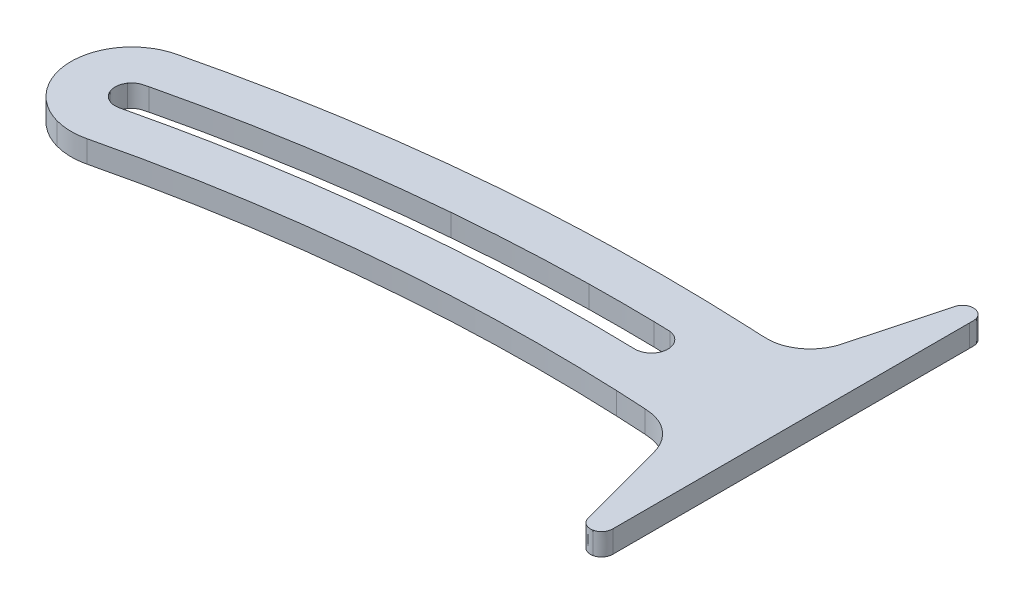
SolidWorks part; units mm, degrees
ref_plane "Front Plane" through (0, 0, 0) normal (0, 0, 1) x (1, 0, 0)
ref_plane "Top Plane" through (0, 0, 0) normal (0, 1, 0) x (1, 0, 0)
ref_plane "Right Plane" through (0, 0, 0) normal (1, 0, 0) x (0, 0, -1)
sketch "Imported Profile" plane through (0, 0, 0) normal (0, 1, 0) x (1, 0, 0)
  spline S0 degree 3 poles (12.8991, 25.236) (15.9171, 24.4093) (18.7007, 24.3473) (21.7531, 25.0501) knots 0 0 0 0 1 1 1 1
  spline S1 degree 3 poles (21.7531, 25.0501) (67.2422, 35.9573) (114.0335, 40.4773) (160.7696, 38.4929) knots 0 0 0 0 1 1 1 1
  spline S2 degree 3 poles (160.7696, 38.4929) (163.6635, 38.3689) (166.5574, 38.2174) (169.4444, 38.0449) knots 0 0 0 0 1 1 1 1
  spline S3 degree 3 poles (169.4444, 38.0449) (172.5863, 37.8589) (175.1081, 37.0734) (177.5541, 34.9719) knots 0 0 0 0 1 1 1 1
  spline S4 degree 3 poles (177.5541, 34.9719) (178.7254, 33.9728) (179.6419, 32.8428) (180.3929, 31.4993) knots 0 0 0 0 1 1 1 1
  spline S5 degree 3 poles (180.3929, 31.4993) (181.1026, 30.2177) (181.4953, 28.8603) (181.8674, 27.4685) knots 0 0 0 0 1 1 1 1
  spline S6 degree 3 poles (181.8674, 27.4685) (182.6184, 24.6642) (183.3694, 21.8599) (184.1205, 19.0625) knots 0 0 0 0 1 1 1 1
  spline S7 degree 3 poles (184.1205, 19.0625) (184.8715, 16.2582) (185.6225, 13.4539) (186.3735, 10.6495) knots 0 0 0 0 1 1 1 1
  spline S8 degree 3 poles (186.3735, 10.6495) (186.7457, 9.2508) (187.1246, 7.8521) (187.4967, 6.4465) knots 0 0 0 0 1 1 1 1
  spline S9 degree 3 poles (187.4967, 6.4465) (187.6827, 5.7506) (187.8756, 5.0478) (188.0617, 4.345) knots 0 0 0 0 1 1 1 1
  spline S10 degree 3 poles (188.0617, 4.345) (188.2477, 3.6491) (188.3786, 2.9463) (188.6335, 2.2642) knots 0 0 0 0 1 1 1 1
  spline S11 degree 3 poles (188.6335, 2.2642) (189.1847, 0.8172) (190.7006, -0.0165) (192.2233, 0.2798) knots 0 0 0 0 1 1 1 1
  spline S12 degree 3 poles (192.2233, 0.2798) (193.7874, 0.5968) (194.7796, 1.9335) (194.7796, 3.4975) knots 0 0 0 0 1 1 1 1
  spline S13 degree 3 poles (194.7796, 3.4975) (194.7796, 6.3983) (194.7796, 9.2991) (194.7796, 12.1998) knots 0 0 0 0 1 1 1 1
  spline S14 degree 3 poles (194.7796, 12.1998) (194.7796, 35.5507) (194.7796, 58.9084) (194.7796, 82.2593) knots 0 0 0 0 1 1 1 1
  spline S15 degree 3 poles (194.7796, 82.2593) (194.7796, 88.0608) (194.7796, 93.8624) (194.7796, 99.6708) knots 0 0 0 0 1 1 1 1
  spline S16 degree 3 poles (194.7796, 99.6708) (194.7796, 101.1178) (194.7796, 102.5716) (194.7796, 104.0185) knots 0 0 0 0 1 1 1 1
  spline S17 degree 3 poles (194.7796, 104.0185) (194.7796, 104.742) (194.7796, 105.4724) (194.7796, 106.1958) knots 0 0 0 0 1 1 1 1
  spline S18 degree 3 poles (194.7796, 106.1958) (194.7796, 106.9193) (194.8485, 107.6152) (194.6072, 108.3387) knots 0 0 0 0 1 1 1 1
  spline S19 degree 3 poles (194.6072, 108.3387) (194.1043, 109.7994) (192.6229, 110.6882) (191.0932, 110.4402) knots 0 0 0 0 1 1 1 1
  spline S20 degree 3 poles (191.0932, 110.4402) (190.2595, 110.3027) (189.6807, 109.9717) (189.1433, 109.3171) knots 0 0 0 0 1 1 1 1
  spline S21 degree 3 poles (189.1433, 109.3171) (188.6541, 108.7176) (188.5094, 108.0424) (188.3234, 107.3327) knots 0 0 0 0 1 1 1 1
  spline S22 degree 3 poles (188.3234, 107.3327) (186.8213, 101.731) (185.3193, 96.1292) (183.8172, 90.5206) knots 0 0 0 0 1 1 1 1
  spline S23 degree 3 poles (183.8172, 90.5206) (183.0662, 87.7232) (182.3909, 84.912) (181.5641, 82.1353) knots 0 0 0 0 1 1 1 1
  spline S24 degree 3 poles (181.5641, 82.1353) (180.7097, 79.2483) (178.8563, 76.7678) (176.3413, 75.121) knots 0 0 0 0 1 1 1 1
  spline S25 degree 3 poles (176.3413, 75.121) (172.2486, 72.4477) (169.1411, 73.0678) (164.7796, 73.2676) knots 0 0 0 0 1 1 1 1
  spline S26 degree 3 poles (164.7796, 73.2676) (145.3906, 74.1909) (126.0843, 74.1289) (106.7022, 73.0126) knots 0 0 0 0 1 1 1 1
  spline S27 degree 3 poles (106.7022, 73.0126) (83.2893, 71.6621) (60.2485, 68.6924) (37.2422, 64.1724) knots 0 0 0 0 1 1 1 1
  spline S28 degree 3 poles (37.2422, 64.1724) (29.3115, 62.6153) (21.4154, 60.9065) (13.5537, 58.9979) knots 0 0 0 0 1 1 1 1
  spline S29 degree 3 poles (13.5537, 58.9979) (13.4434, 58.9679) (13.3332, 58.9429) (13.2298, 58.9154) knots 0 0 0 0 1 1 1 1
  spline S30 degree 3 poles (13.2298, 58.9154) (13.0093, 58.8604) (12.7889, 58.7984) (12.5753, 58.7294) knots 0 0 0 0 1 1 1 1
  spline S31 degree 3 poles (12.5753, 58.7294) (12.1274, 58.5914) (11.6933, 58.4469) (11.2661, 58.2744) knots 0 0 0 0 1 1 1 1
  spline S32 degree 3 poles (11.2661, 58.2744) (10.3773, 57.9229) (9.5298, 57.5027) (8.7099, 57.0135) knots 0 0 0 0 1 1 1 1
  spline S33 degree 3 poles (8.7099, 57.0135) (6.9735, 55.9731) (5.5197, 54.726) (4.2313, 53.1688) knots 0 0 0 0 1 1 1 1
  spline S34 degree 3 poles (4.2313, 53.1688) (1.7439, 50.1716) (0.3383, 46.4302) (0.2281, 42.5373) knots 0 0 0 0 1 1 1 1
  spline S35 degree 3 poles (0.2281, 42.5373) (-0.0062, 34.5515) (5.2166, 27.4271) (12.8991, 25.236) knots 0 0 0 0 1 1 1 1
  spline S36 degree 3 poles (153.0044, 51.4685) (156.4908, 51.3706) (158.8886, 54.9191) (157.5036, 58.1161) knots 0 0 0 0 1 1 1 1
  spline S37 degree 3 poles (157.5036, 58.1161) (156.8353, 59.6595) (155.409, 60.7344) (153.7416, 60.948) knots 0 0 0 0 1 1 1 1
  spline S38 degree 3 poles (153.7416, 60.948) (153.2937, 61.01) (149.5386, 61.072) (149.0907, 61.079) knots 0 0 0 0 1 1 1 1
  spline S39 degree 3 poles (149.0907, 61.079) (142.8482, 61.196) (136.5988, 61.203) (130.3494, 61.094) knots 0 0 0 0 1 1 1 1
  spline S40 degree 3 poles (130.3494, 61.094) (117.7059, 60.8805) (105.1106, 60.212) (92.5154, 59.0889) knots 0 0 0 0 1 1 1 1
  spline S41 degree 3 poles (92.5154, 59.0889) (67.2422, 56.8358) (42.4581, 52.8051) (17.7706, 46.9484) knots 0 0 0 0 1 1 1 1
  spline S42 degree 3 poles (17.7706, 46.9484) (16.1652, 46.5694) (14.7734, 46.2387) (13.7329, 44.6953) knots 0 0 0 0 1 1 1 1
  spline S43 degree 3 poles (13.7329, 44.6953) (12.8234, 43.3517) (12.6649, 41.6499) (13.3057, 40.1547) knots 0 0 0 0 1 1 1 1
  spline S44 degree 3 poles (13.3057, 40.1547) (13.9672, 38.6044) (15.4072, 37.5226) (17.0816, 37.309) knots 0 0 0 0 1 1 1 1
  spline S45 degree 3 poles (17.0816, 37.309) (17.8808, 37.2055) (18.6112, 37.359) (19.3691, 37.5365) knots 0 0 0 0 1 1 1 1
  spline S46 degree 3 poles (19.3691, 37.5365) (20.127, 37.7225) (20.8849, 37.9015) (21.6429, 38.074) knots 0 0 0 0 1 1 1 1
  spline S47 degree 3 poles (21.6429, 38.074) (27.7269, 39.5002) (33.8316, 40.8094) (39.9708, 42.0151) knots 0 0 0 0 1 1 1 1
  spline S48 degree 3 poles (39.9708, 42.0151) (52.38, 44.4405) (64.8375, 46.4111) (77.3914, 47.9269) knots 0 0 0 0 1 1 1 1
  spline S49 degree 3 poles (77.3914, 47.9269) (102.5751, 50.9655) (127.6485, 52.1368) (153.0044, 51.4685) knots 0 0 0 0 1 1 1 1
extrude "Boss-Extrude1" add sketch "Imported Profile" along normal blind 6.35
sketch "Sketch1" plane through (0, 6.35, 0) normal (0, 1, 0) x (1, 0, 0)
  line L0 (191.616, 107.3087) -> (191.616, 3.4975) construction
  line L1 (194.7796, 107.3087) -> (194.7796, 3.4975) construction
  line L2 (188.4524, 107.3087) -> (188.4524, 3.4975) construction
  line L5 (194.7796, 12.1998) -> (194.7796, 82.2593) construction
  line L6 (194.7796, 55.4031) -> (171.9196, 55.4031) construction
  arc A0 (194.7796, 107.3087) -> (188.4524, 107.3087) centre (191.616, 107.3087) ccw construction
  arc A1 (188.4524, 3.4975) -> (194.7796, 3.4975) centre (191.616, 3.4975) ccw construction
  spline S0 degree 3 poles (194.6072, 108.3387) (194.1043, 109.7994) (192.6229, 110.6882) (191.0932, 110.4402) knots 0 0 0 0 1 1 1 1 construction
  spline S1 degree 3 poles (192.2233, 0.2798) (193.7874, 0.5968) (194.7796, 1.9335) (194.7796, 3.4975) knots 0 0 0 0 1 1 1 1 construction
  point P2 (191.616, 55.4031)
  dimension "D1" = 22.86
  dimension "D2" = 6.3272
sketch3d "3DSketch1"
  line L0 (171.9196, 6.35, -55.4031) -> (171.9196, 0, -55.4031) construction
sketch "Sketch2" plane through (0, 0, 0) normal (0, -1, 0) x (1, 0, 0)
  line L0 (131.3895, -51.8859) -> (96.6153, -50.1813) construction
  line L1 (114.0024, -51.0336) -> (113.5363, -60.5407) construction
  line L2 (41.428, -42.497) -> (69.6198, -47.1272) construction
  line L3 (55.5239, -44.8121) -> (53.9795, -54.2158) construction
  circle A0 centre (153.1375, -56.2248) radius 4.7582 construction
  circle A1 centre (17.6798, -42.0304) radius 4.7593 construction
  spline S0 degree 3 poles (153.0044, -51.4685) (156.4908, -51.3706) (158.8886, -54.9191) (157.5036, -58.1161) knots 0 0 0 0 1 1 1 1 construction
  spline S2 degree 3 poles (17.0816, -37.309) (17.8808, -37.2055) (18.6112, -37.359) (19.3691, -37.5365) knots 0 0 0 0 1 1 1 1 construction
  spline S3 degree 3 poles (13.7329, -44.6953) (12.8234, -43.3517) (12.6649, -41.6499) (13.3057, -40.1547) knots 0 0 0 0 1 1 1 1 construction
  spline S4 degree 3 poles (153.1375, -56.2248) (107.1548, -57.4301) (62.0117, -52.6466) (17.6798, -42.0304) knots 0 0 0 0 1 1 1 1
  spline S7 degree 3 poles (77.3914, -47.9269) (102.5751, -50.9655) (127.6485, -52.1368) (153.0044, -51.4685) knots 0 0 0 0 1 1 1 1 construction
  spline S8 degree 3 poles (130.3494, -61.094) (117.7059, -60.8805) (105.1106, -60.212) (92.5154, -59.0889) knots 0 0 0 0 1 1 1 1 construction
  spline S10 degree 3 poles (92.5154, -59.0889) (67.2422, -56.8358) (42.4581, -52.8051) (17.7706, -46.9484) knots 0 0 0 0 1 1 1 1 construction
  spline S11 degree 3 poles (39.9708, -42.0151) (52.38, -44.4405) (64.8375, -46.4111) (77.3914, -47.9269) knots 0 0 0 0 1 1 1 1 construction
  point P16 (114.0024, -51.0336)
  point P18 (113.7694, -55.7872)
  point P26 (55.5239, -44.8121)
  point P32 (0, 0)
  point P33 (66.2126, -56.0778)
  point P34 (55.5239, -44.8121)
  point P37 (53.9795, -54.2158)
  point P38 (54.7517, -49.5139)
  dimension "D1" = 39.002
  dimension "D2" = 33.8811
